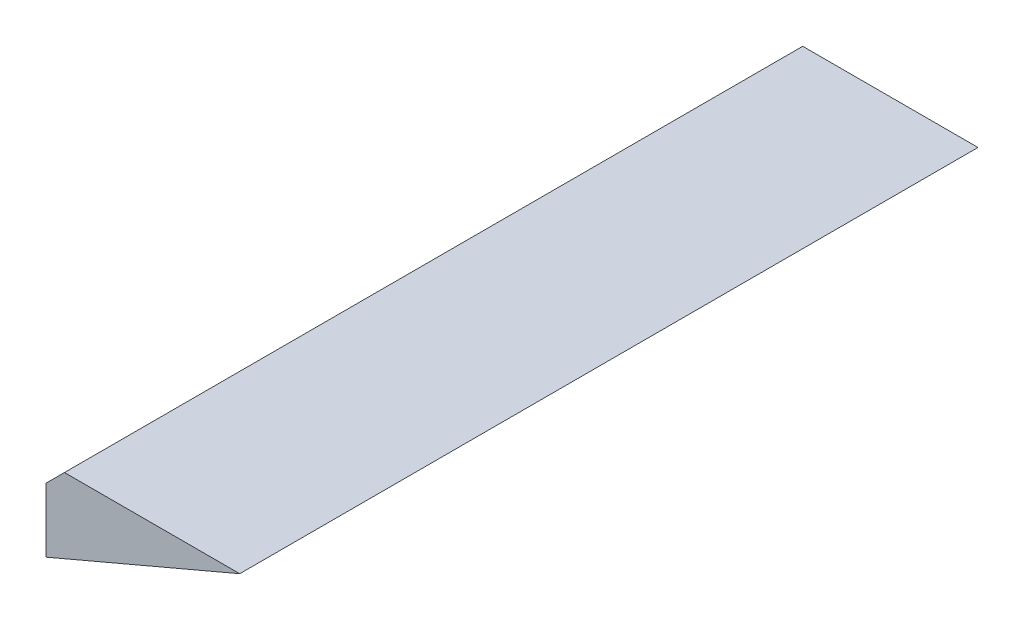
SolidWorks part; units mm, degrees
ref_plane "Ebene vorne" through (0, 0, 0) normal (0, 0, 1) x (1, 0, 0)
ref_plane "Ebene oben" through (0, 0, 0) normal (0, 1, 0) x (1, 0, 0)
ref_plane "Ebene rechts" through (0, 0, 0) normal (1, 0, 0) x (0, 0, -1)
sketch "Skizze1" plane through (0, 0, 0) normal (0, 0, 1) x (1, 0, 0)
  line L2 (-188.5516, 146.6266) -> (-188.5516, 124.273) construction
  line L3 (-188.5516, 146.6266) -> (-136.0693, 146.6266) construction
  line L6 (-188.5516, 146.6266) -> (-188.5516, 124.273)
  line L7 (-188.5516, 146.6266) -> (-136.0693, 146.6266)
  line L8 (-188.5516, 124.273) -> (-136.0693, 146.6266) construction
  line L9 (-188.5516, 124.273) -> (-136.0693, 146.6266)
extrude "Aufsatz-Linear austragen1" add sketch "Skizze1" along normal blind 200
chamfer "Fase1" distance 5 angle 45 1 edges at (-188.5516, 146.6266, 100)
